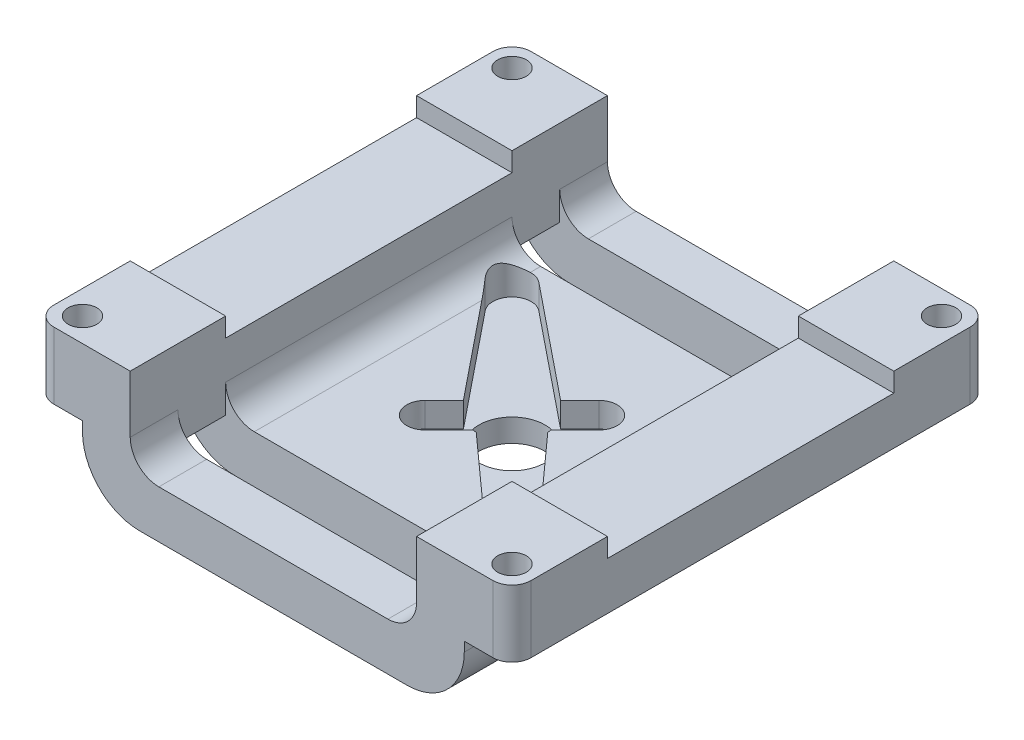
SolidWorks part; units mm, degrees
ref_plane "前视基准面" through (0, 0, 0) normal (0, 0, 1) x (1, 0, 0)
ref_plane "上视基准面" through (0, 0, 0) normal (0, 1, 0) x (1, 0, 0)
ref_plane "右视基准面" through (0, 0, 0) normal (1, 0, 0) x (0, 0, -1)
sketch "草图1" plane through (0, 0, 0) normal (0, 0, 1) x (1, 0, 0)
  line L0 (-45, 4.3806) -> (-35, 4.3806)
  line L1 (-35, 4.3806) -> (-35, -2.6194)
  line L2 (-35, -2.6194) -> (-5, -2.6194)
  line L3 (-5, -2.6194) -> (-5, 4.3806)
  line L4 (-5, 4.3806) -> (5, 4.3806)
  line L5 (5, 4.3806) -> (5, -0.6194)
  line L6 (5, -0.6194) -> (0, -0.6194)
  line L7 (0, -0.6194) -> (0, -7.6194)
  line L8 (0, -7.6194) -> (-40, -7.6194)
  line L9 (-40, -7.6194) -> (-40, -0.6194)
  line L10 (-40, -0.6194) -> (-45, -0.6194)
  line L11 (-45, -0.6194) -> (-45, 4.3806)
  dimension "D1" = 5
  dimension "D2" = 5
  dimension "D3" = 5
  dimension "D4" = 5
  dimension "D5" = 5
  dimension "D6" = 30
  dimension "D7" = 7
  dimension "D8" = 7
  dimension "D9" = 50
  dimension "D10" = 10
extrude "凸台-拉伸1" add sketch "草图1" along normal blind 50
sketch "草图2" plane through (0, -2.6194, 0) normal (0, 1, 0) x (1, 0, 0)
  circle A0 centre (-20, -25) radius 3.45
  point P19 (-20, -25)
extrude "切除-拉伸1" cut sketch "草图2" against normal blind 50
sketch "草图3" plane through (0, 4.3806, 0) normal (0, 1, 0) x (1, 0, 0)
  line L0 (-5, -50) -> (-5, -40)
  line L1 (-5, -50) -> (-5, 0) construction
  line L2 (-5, -40) -> (5, -40)
  line L3 (5, -50) -> (5, 0) construction
  line L4 (5, -40) -> (5, -50)
  line L5 (5, -50) -> (-5, -50)
  line L7 (-35, -40) -> (-35, -50)
  line L8 (-45, -40) -> (-35, -40)
  line L9 (-35, -50) -> (-45, -50)
  line L10 (-45, -50) -> (-45, -40)
  line L11 (-35, -10) -> (-45, -10)
  line L12 (-35, 0) -> (-35, -10)
  line L13 (-45, -10) -> (-45, 0)
  line L14 (-45, 0) -> (-35, 0)
  line L15 (-5, -10) -> (-5, 0)
  line L16 (5, -10) -> (-5, -10)
  line L17 (-5, 0) -> (5, 0)
  line L18 (5, 0) -> (5, -10)
  point P27 (-20, -25)
  dimension "D1" = 4
extrude "凸台-拉伸2" add sketch "草图3" along normal blind 2
fillet "圆角1" radius 6 1 edges at (-40, -7.6194, 25) type face fillet first side face at (-23.45, -7.6194, 25) second side face at (-40, -4.1194, 25)
fillet "圆角2" radius 6 1 edges at (0, -7.6194, 25) type face fillet first side face at (0, -4.1194, 25) second side face at (-23.45, -7.6194, 25)
fillet "圆角3" radius 3 1 edges at (-5, -2.6194, 25) type face fillet first side face at (-20, -2.6194, 28.45) second side face at (-5, 3.6306, 25)
fillet "圆角4" radius 3 1 edges at (-35, -2.6194, 25) type face fillet first side face at (-20, -2.6194, 28.45) second side face at (-35, 3.6306, 25)
sketch "草图4" plane through (0, -0.6194, 0) normal (0, -1, 0) x (1, 0, 0)
  line L0 (5, 50) -> (2.5, 50)
  line L1 (0, 50) -> (5, 50) construction
sketch "草图5" plane through (0, -0.6194, 0) normal (0, -1, 0) x (1, 0, 0)
  line L0 (5, 50) -> (2.5, 50) construction
  line L1 (5, 50) -> (5, 0) construction
  line L2 (5, 25) -> (-45, 25) construction
  line L3 (-45, 50) -> (-45, 0) construction
  line L4 (-20, 25) -> (-20, 36.4253) construction
  circle A0 centre (2.5, 47.5) radius 1.5
  circle A1 centre (2.5, 2.5) radius 1.5
  circle A2 centre (-42.5, 2.5) radius 1.5
  circle A3 centre (-42.5, 47.5) radius 1.5
  dimension "D1" = 2.5
  dimension "D2" = 2.5
extrude "切除-拉伸2" cut sketch "草图5" against normal blind 23
fillet "圆角5" radius 2 1 edges at (5, 2.8806, 50) type face fillet first side face at (-20, -0.2274, 50) second side face at (5, 4.1306, 25)
fillet "圆角6" radius 2 1 edges at (5, 2.8806, 0) type face fillet first side face at (5, 4.1306, 24.5) second side face at (-20, -0.2274, 0)
fillet "圆角7" radius 2 1 edges at (-45, 2.8806, 0) type face fillet first side face at (-20.25, -0.2274, 0) second side face at (-45, 4.1306, 25)
fillet "圆角8" radius 2 1 edges at (-45, 2.8806, 50) type face fillet first side face at (-45, 4.1306, 25.5) second side face at (-20.25, -0.2274, 50)
sketch "草图7" plane through (0, -7.6194, 0) normal (0, -1, 0) x (1, 0, 0)
  line L2 (-42.4691, 45) -> (1.8886, 45)
  line L3 (1.8886, 45) -> (1.8886, 40)
  line L4 (1.8886, 40) -> (-42.4691, 40)
  line L5 (-42.4691, 40) -> (-42.4691, 45)
  line L6 (-34, 50) -> (-6, 50) construction
  line L7 (-42.4691, 10) -> (-42.4691, 5)
  line L8 (1.8886, 10) -> (-42.4691, 10)
  line L9 (1.8886, 5) -> (1.8886, 10)
  line L10 (-42.4691, 5) -> (1.8886, 5)
  point P9 (1.8886, 42.5)
  dimension "D1" = 5
  dimension "D2" = 7.5
extrude "切除-拉伸4" cut sketch "草图7" against normal blind 5
sketch "草图8" plane through (0, 6.3806, 0) normal (0, 1, 0) x (1, 0, 0)
  line L0 (-8, -40) -> (-5, -40)
  line L1 (-5, -40) -> (-5, -45)
  line L2 (-5, -40) -> (-5, -50) construction
  line L3 (-5, -45) -> (-35, -45)
  line L4 (-35, -50) -> (-35, -40) construction
  line L5 (-35, -45) -> (-35, -40)
  line L6 (-35, -40) -> (-8, -40)
  line L7 (-32, -25) -> (-29.6459, -25)
  line L8 (-32, -10) -> (-32, -40) construction
  line L9 (-35, -10) -> (-8, -10)
  line L10 (-35, -5) -> (-35, -10)
  line L11 (-5, -5) -> (-35, -5)
  line L12 (-5, -10) -> (-5, -5)
  line L13 (-8, -10) -> (-5, -10)
  line M6 (-35, -50) -> (-35, -40)
extrude "切除-拉伸5" cut sketch "草图8" against normal blind 31 contours L6 L3 L1 L0 M6 | L9 L13 L12 L11 L10 region at (-20, 6.3806, 42.5) region at (-20, 6.3806, 7.5)
sketch "草图9" plane through (0, -2.6194, 0) normal (0, 1, 0) x (1, 0, 0)
  line L0 (-22.4395, -27.4395) -> (-20, -25) construction
  line L1 (-22.4395, -22.5605) -> (-17.5605, -27.4395) construction
  line L2 (-16.7827, -19.0957) -> (-18.7979, -21.1109)
  line L3 (-14.0957, -21.7827) -> (-16.6203, -24.3073)
  line L4 (-30.6579, -11.5295) -> (-18.7979, -21.1109)
  line L5 (-8.2954, -33.8801) -> (-16.5641, -24.6888)
  line L6 (-33.4705, -14.3421) -> (-23.8891, -26.2021)
  line L7 (-11.1199, -36.7046) -> (-20.3112, -28.4359)
  line L8 (-23.2173, -30.9043) -> (-20.6927, -28.3797)
  line L9 (-25.9043, -28.2173) -> (-23.8891, -26.2021)
  arc A6 (-14.0957, -21.7827) -> (-16.7827, -19.0957) centre (-15.4392, -20.4392) ccw
  arc A9 (-30.6579, -11.5295) -> (-33.4705, -14.3421) centre (-31.9147, -13.0853) ccw
  arc A10 (-11.1199, -36.7046) -> (-8.2954, -33.8801) centre (-9.7823, -35.2177) ccw
  arc A11 (-16.5641, -24.6888) -> (-16.6203, -24.3073) centre (-20, -25) ccw
  arc A12 (-23.2173, -30.9043) -> (-25.9043, -28.2173) centre (-24.5608, -29.5608) cw
  arc A13 (-20.6927, -28.3797) -> (-20.3112, -28.4359) centre (-20, -25) ccw
  dimension "D1" = 3.8
  dimension "D4" = 4
  dimension "D5" = 16.85
  dimension "D6" = 14.45
  dimension "D2" = 6.45
  dimension "D3" = 4
extrude "切除-拉伸6" cut sketch "草图9" against normal mid plane 5.2
